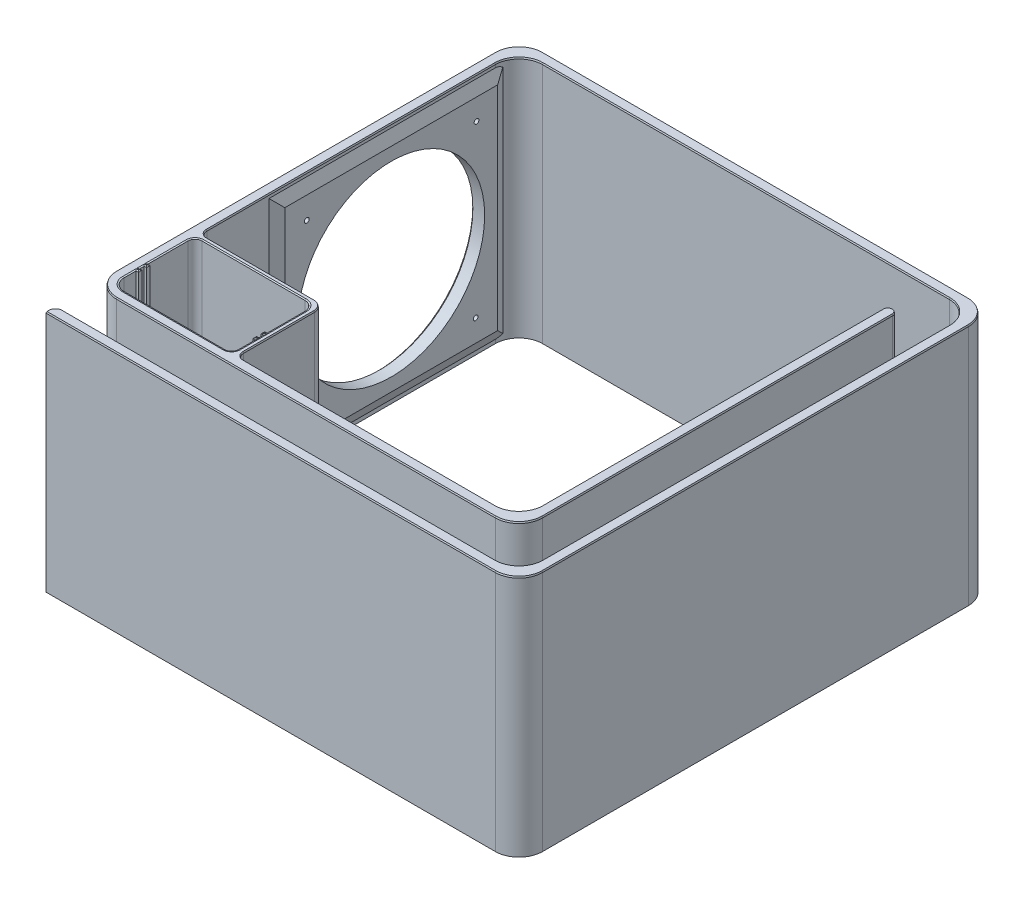
SolidWorks part; units mm, degrees
ref_plane "Front Plane" through (0, 0, 0) normal (0, 0, 1) x (1, 0, 0)
ref_plane "Top Plane" through (0, 0, 0) normal (0, 1, 0) x (1, 0, 0)
ref_plane "Right Plane" through (0, 0, 0) normal (1, 0, 0) x (0, 0, -1)
sketch "Sketch1" plane through (0, 0, 0) normal (0, 1, 0) x (1, 0, 0)
  line L0 (-100, 90) -> (-100, -70.2)
  line L1 (-90, 100) -> (90, 100)
  line L2 (100, 90) -> (100, -90)
  line L3 (90, -100) -> (-100, -100)
  line L4 (-100, -100) -> (-100, -99)
  line L5 (-97, -96) -> (86, -96)
  line L6 (86, 96) -> (-86, 96)
  line L7 (-96, 86) -> (-96, -36)
  line L8 (-91, -76) -> (-48.5, -76)
  line L9 (76, -66) -> (76, 78)
  line L10 (-90.2, -80) -> (70, -80)
  line L11 (96, -86) -> (96, 86)
  line L12 (80, 78) -> (80, -70)
  line L13 (-99, -86) -> (86, -86) construction
  line L14 (86, -86) -> (86, 86) construction
  line L15 (-93, -41) -> (-49.5, -41)
  line L16 (-45.5, -45) -> (-45.5, -61)
  line L18 (-43.5, -73) -> (-43.5, -43)
  line L19 (-47.5, -39) -> (-93, -39)
  line L20 (-96, -44) -> (-96, -61)
  line L21 (-40.5, -76) -> (66, -76)
  line L22 (-96, -61) -> (-95, -61)
  line L23 (-95, -61) -> (-95, -62.5)
  line L24 (-95, -62.5) -> (-96, -62.5)
  line L25 (-96, -64.4) -> (-95, -64.4)
  line L26 (-95, -64.4) -> (-95, -65.9)
  line L27 (-95, -65.9) -> (-96, -65.9)
  line L28 (-96, -62.5) -> (-96, -64.4)
  line L29 (-96, -65.9) -> (-96, -71)
  line L30 (-45.5, -61) -> (-46.5, -61)
  line L31 (-46.5, -61) -> (-46.5, -62.5)
  line L32 (-46.5, -62.5) -> (-45.5, -62.5)
  line L33 (-45.5, -65.9) -> (-46.5, -65.9)
  line L34 (-46.5, -65.9) -> (-46.5, -64.4)
  line L35 (-46.5, -64.4) -> (-45.5, -64.4)
  line L36 (-45.5, -62.5) -> (-45.5, -64.4)
  line L37 (-45.5, -65.9) -> (-45.5, -73)
  arc A1 (-96, -71) -> (-91, -76) centre (-91, -71) ccw
  arc A2 (66, -76) -> (76, -66) centre (66, -66) ccw
  arc A3 (-86, 96) -> (-96, 86) centre (-86, 86) ccw
  arc A4 (-100, 90) -> (-90, 100) centre (-90, 90) cw
  arc A5 (100, -90) -> (90, -100) centre (90, -90) cw
  arc A6 (86, -96) -> (96, -86) centre (86, -86) ccw
  arc A7 (80, -70) -> (70, -80) centre (70, -70) cw
  arc A8 (86, 96) -> (96, 86) centre (86, 86) cw
  arc A9 (90, 100) -> (100, 90) centre (90, 90) cw
  arc A10 (76, 78) -> (80, 78) centre (78, 78) cw
  arc A11 (-100, -99) -> (-97, -96) centre (-97, -99) cw
  arc A12 (-100, -70.2) -> (-90.2, -80) centre (-90.2, -70.2) ccw
  arc A13 (-43.5, -43) -> (-47.5, -39) centre (-47.5, -43) ccw
  arc A14 (-49.5, -41) -> (-45.5, -45) centre (-49.5, -45) cw
  arc A15 (-40.5, -76) -> (-43.5, -73) centre (-40.5, -73) cw
  arc A16 (-93, -39) -> (-96, -36) centre (-93, -36) cw
  arc A17 (-45.5, -73) -> (-48.5, -76) centre (-48.5, -73) cw
  arc A18 (-93, -41) -> (-96, -44) centre (-93, -44) ccw
  point P49 (-45.5, -41)
  point P52 (-43.5, -76)
  point P57 (-45.5, -76)
  point P60 (-96, -41)
  point P69 (-95.5, -64.4)
  dimension "D6" = 9.8
  dimension "D7" = 10
  dimension "D8" = 10
  dimension "D9" = 10
  dimension "D10" = 10
  dimension "D16" = 10
  dimension "D17" = 10
  dimension "D18" = 10
  dimension "D19" = 10
  dimension "D22" = 3
  dimension "D25" = 5
  dimension "D30" = 4
  dimension "D31" = 3
  dimension "D32" = 3
  dimension "D1" = 4
  dimension "D2" = 4
  dimension "D3" = 4
  dimension "D4" = 16
  dimension "D5" = 4
  dimension "D11" = 200
  dimension "D12" = 200
  dimension "D13" = 4
  dimension "D14" = 16
  dimension "D15" = 4
  dimension "D20" = 2
  dimension "D21" = 16
  dimension "D23" = 100
  dimension "D24" = 100
  dimension "D26" = 35
  dimension "D27" = 2
  dimension "D28" = 2
  dimension "D29" = 50.5
  dimension "D33" = 1.5
  dimension "D34" = 1.9
  dimension "D35" = 1
  dimension "D36" = 20
  dimension "D37" = 1.9
  dimension "D38" = 1
extrude "Boss-Extrude1" add sketch "Sketch1" along normal blind 103
sketch "Sketch2" plane through (-100, 0, 0) normal (-1, 0, 0) x (0, 0, 1)
  line L0 (-90, 0) -> (70.2, 0) construction
  line L1 (-90, 103) -> (-90, 0) construction
  line L2 (5.2199, 6.2801) -> (-85.2199, 96.7199) construction
  line L3 (-79.2811, 12.2189) -> (-0.7189, 90.7811) construction
  circle A0 centre (-40, 51.5) radius 39.5
  circle A1 centre (-4.2911, 15.7911) radius 1
  circle A2 centre (-76.0624, 87.5624) radius 1
  circle A3 centre (-4.2911, 87.2089) radius 1
  circle A4 centre (-75.7089, 15.7911) radius 1
  dimension "D1" = 79
  dimension "D9" = 2
  dimension "D2" = 51.5
  dimension "D3" = 50
  dimension "D4" = 101.5
  dimension "D5" = 50.5
  dimension "D6" = 45
  dimension "D7" = 101
  dimension "D8" = 50.5
extrude "Cut-Extrude1" cut sketch "Sketch2" against normal up to next
sketch "Sketch3" plane through (-96, 0, 0) normal (1, 0, 0) x (0, 0, -1)
  line L1 (-5, 6.5) -> (85, 6.5)
  line L2 (-5, 6.5) -> (-5, 96.5)
  line L3 (-5, 96.5) -> (85, 96.5)
  line L4 (85, 6.5) -> (85, 96.5)
  line L5 (-5, 6.5) -> (85, 96.5) construction
  line L6 (-5, 96.5) -> (85, 6.5) construction
  circle A0 centre (40, 51.5) radius 39.5
  point P0 (40, 51.5)
  dimension "D3" = 79
  dimension "D1" = 90
  dimension "D2" = 90
extrude "Boss-Extrude2" add sketch "Sketch3" along normal blind 2
chamfer "Chamfer1" distance 2 angle 67 4 edges at (-96, 6.5, -40) (-96, 51.5, 5) (-96, 96.5, -40) (-96, 51.5, -85)
sketch "Sketch6" plane through (-96, 0, 0) normal (-1, 0, 0) x (0, 0, 1)
  circle A0 centre (-75.7089, 15.7911) radius 1 construction
  circle A1 centre (-4.2911, 15.7911) radius 1 construction
  circle A2 centre (-76.0624, 87.5624) radius 1 construction
  circle A3 centre (-4.2911, 87.2089) radius 1 construction
  circle A4 centre (-75.7089, 15.7911) radius 1
  circle A5 centre (-4.2911, 15.7911) radius 1
  circle A6 centre (-76.0624, 87.5624) radius 1
  circle A7 centre (-4.2911, 87.2089) radius 1
extrude "Cut-Extrude2" cut sketch "Sketch6" against normal up to next
chamfer "Chamfer4" distance 1 angle 45 1 edges at (-100, 51.5, -0.5)
chamfer "Chamfer5" distance 0.2 angle 72 106 edges at (76, 0, -6) (73.0711, 0, 73.0711) (-69.75, 0, 76) (-94.5355, 0, 74.5355) (-96, 0, -25) (-93.0711, 0, -93.0711) (0, 0, -96) (93.0711, 0, -93.0711) (96, 0, 0) (93.0711, 0, 93.0711) (-5.5, 0, 96) (-99.1213, 0, 96.8787) (-100, 0, 99.5) (-5, 0, 100) (97.0711, 0, 97.0711) (100, 0, 0) (97.0711, 0, -97.0711) (0, 0, -100) (-97.0711, 0, -97.0711) (-100, 0, -9.9) (-97.1296, 0, 77.1296) (-10.1, 0, 80) (77.0711, 0, 77.0711) (80, 0, -4) (78, 0, -80) (80, 103, -4) (77.0711, 103, 77.0711) (-10.1, 103, 80) (-97.1296, 103, 77.1296) (-100, 103, -9.9) (-97.0711, 103, -97.0711) (0, 103, -100) (97.0711, 103, -97.0711) (100, 103, 0) (97.0711, 103, 97.0711) (-5, 103, 100) (-100, 103, 99.5) (-99.1213, 103, 96.8787) (-5.5, 103, 96) (93.0711, 103, 93.0711) (96, 103, 0) (93.0711, 103, -93.0711) (0, 103, -96) (-93.0711, 103, -93.0711) (-96, 103, -25) (-94.5355, 103, 74.5355) (-69.75, 103, 76) (73.0711, 103, 73.0711) (76, 103, -6) (78, 103, -80) (-95.5, 0, 65.9) (-95, 0, 65.15) (-95.5, 0, 64.4) (-96, 0, 63.45) (-95.5, 0, 62.5) (-95, 0, 61.75) (-95.5, 0, 61) (-96, 0, 52.5) (-95.1213, 0, 41.8787) (-71.25, 0, 41) (-46.6716, 0, 42.1716) (-45.5, 0, 53) (-46, 0, 61) (-46.5, 0, 61.75) (-46, 0, 62.5) (-45.5, 0, 63.45) (-46, 0, 64.4) (-46.5, 0, 65.15) (-46, 0, 65.9) (-45.5, 0, 69.45) (-46.3787, 0, 75.1213) (-96, 0, 68.45) (12.75, 0, 76) (-42.6213, 0, 75.1213) (-43.5, 0, 58) (-44.6716, 0, 40.1716) (-70.25, 0, 39) (-95.1213, 0, 38.1213) (-46.3787, 103, 75.1213) (-45.5, 103, 69.45) (-46, 103, 65.9) (-46.5, 103, 65.15) (-46, 103, 64.4) (-45.5, 103, 63.45) (-46, 103, 62.5) (-46.5, 103, 61.75) (-46, 103, 61) (-45.5, 103, 53) (-46.6716, 103, 42.1716) (-71.25, 103, 41) (-95.1213, 103, 41.8787) (-96, 103, 52.5) (-95.5, 103, 61) (-95, 103, 61.75) (-95.5, 103, 62.5) (-96, 103, 63.45) (-95.5, 103, 64.4) (-95, 103, 65.15) (-95.5, 103, 65.9) (-96, 103, 68.45) (-95.1213, 103, 38.1213) (-70.25, 103, 39) (-44.6716, 103, 40.1716) (-43.5, 103, 58) (-42.6213, 103, 75.1213) (12.75, 103, 76)
sketch "Sketch7" plane through (-100, 0, 0) normal (-1, 0, 0) x (0, 0, 1)
  line L0 (52.2, 59.5) -> (52.2, 29.5) construction
  line L1 (62.2, 59.5) -> (62.2, 29.5)
  line L2 (42.2, 59.5) -> (42.2, 29.5)
  line L5 (-90, 0.2) -> (70.2, 0.2) construction
  line L6 (70.2, 102.3845) -> (70.2, 0.2) construction
  arc A0 (62.2, 59.5) -> (42.2, 59.5) centre (52.2, 59.5) ccw
  arc A1 (42.2, 29.5) -> (62.2, 29.5) centre (52.2, 29.5) ccw
  point P2 (52.2, 44.5)
  dimension "D2" = 10
  dimension "D1" = 18
  dimension "D4" = 30
  dimension "D5" = 29.3
extrude "Cut-Extrude3" cut sketch "Sketch7" against normal up to next
fillet "Fillet1" radius 0.4 12 edges at (-96, 69.4836, 52.7719) (-95.7432, 62.8719, 42.7856) (-95.4, 44.5, 42.2) (-100, 44.5, 42.2) (-100, 69.5, 52.2) (-100, 44.5, 62.2) (-95.6457, 26.7493, 42.5857) (-96, 19.5164, 52.7719) (-95.5, 24.7503, 61) (-95, 27.0505, 61.8954) (-100, 19.5, 52.2) (-95, 61.9495, 61.8954)
sketch "Sketch8" plane through (-43.5, 0, 0) normal (1, 0, 0) x (0, 0, -1)
  line L0 (-53, 18.5) -> (-53, 23.5) construction
  line L5 (-54.5, 18.5) -> (-54.5, 23.5)
  line L6 (-51.5, 18.5) -> (-51.5, 23.5)
  line L7 (-43, 102.3845) -> (-43, 0.2) construction
  line L8 (-43, 0) -> (-73, 0) construction
  arc A0 (-54.5, 18.5) -> (-51.5, 18.5) centre (-53, 18.5) ccw
  arc A1 (-51.5, 23.5) -> (-54.5, 23.5) centre (-53, 23.5) ccw
  point P2 (-53, 21)
  dimension "D2" = 1.5
  dimension "D1" = 5
  dimension "D3" = 10
  dimension "D4" = 21
extrude "Cut-Extrude4" cut sketch "Sketch8" against normal up to next
